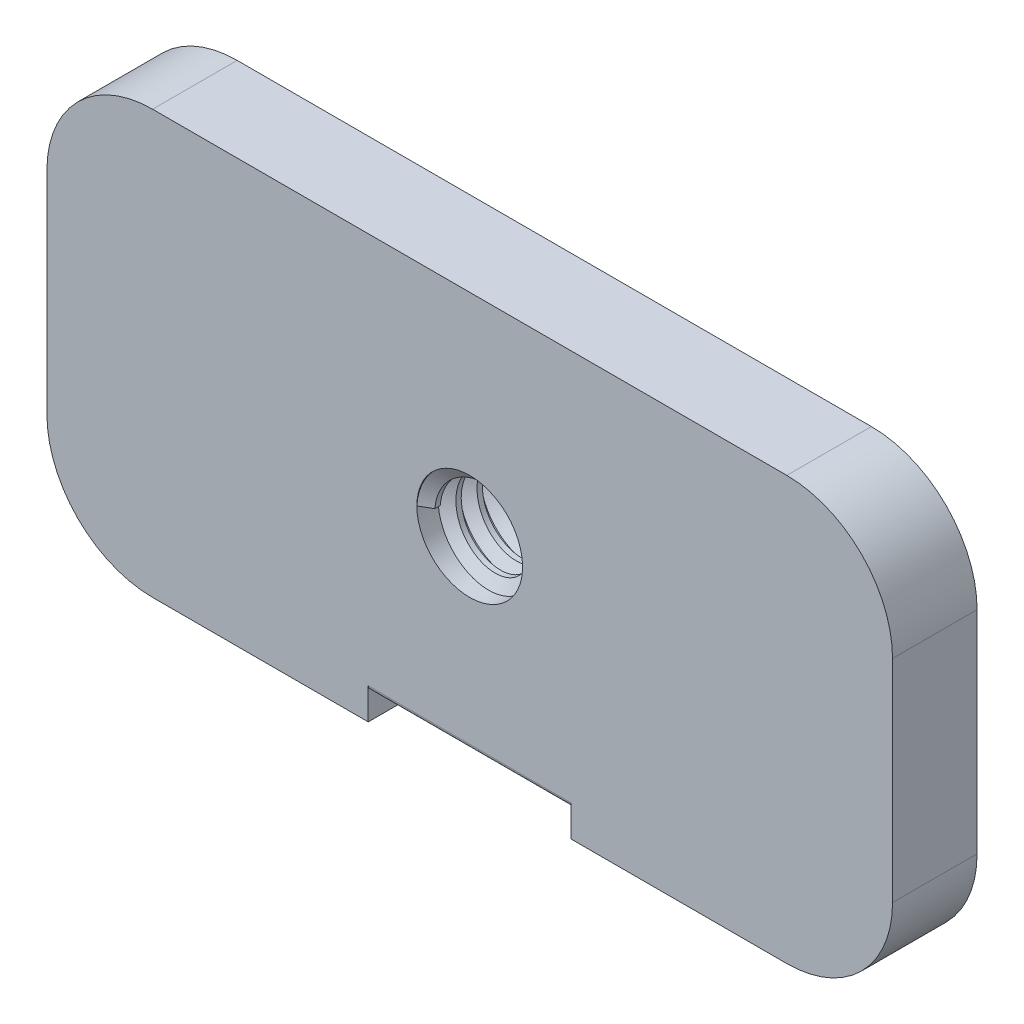
SolidWorks part; units mm, degrees
ref_plane "Front Plane" through (0, 0, 0) normal (0, 0, 1) x (1, 0, 0)
ref_plane "Top Plane" through (0, 0, 0) normal (0, 1, 0) x (1, 0, 0)
ref_plane "Right Plane" through (0, 0, 0) normal (1, 0, 0) x (0, 0, -1)
sketch "Sketch1" plane through (0, 0, 0) normal (0, 0, 1) x (1, 0, 0)
  line L0 (0, -12.7) -> (0, -9.525) construction
  line L1 (-25.4, -12.7) -> (25.4, -12.7)
  line L2 (-25.4, -12.7) -> (-25.4, 12.7)
  line L3 (-25.4, 12.7) -> (25.4, 12.7)
  line L4 (25.4, -12.7) -> (25.4, 12.7)
  line L5 (-25.4, -12.7) -> (25.4, 12.7) construction
  line L6 (-25.4, 12.7) -> (25.4, -12.7) construction
  line L8 (-6.096, -12.7) -> (6.096, -12.7)
  line L9 (-6.096, -12.7) -> (-6.096, -9.525)
  line L10 (-6.096, -9.525) -> (6.096, -9.525)
  line L11 (6.096, -12.7) -> (6.096, -9.525)
  line L12 (-6.096, -12.7) -> (6.096, -9.525) construction
  line L13 (-6.096, -9.525) -> (6.096, -12.7) construction
  circle A0 centre (0, 0) radius 3.175
  point P9 (0, -11.1125)
  dimension "D1" = 6.35
  dimension "D2" = 25.4
  dimension "D3" = 50.8
  dimension "D4" = 3.175
  dimension "D5" = 12.192
extrude "Boss-Extrude1" add sketch "Sketch1" along normal blind 5.08 contours L11 L1 L4 L3 L2 L9 L10 A0 region at (-24.832, 0, 0)
thread "Thread1" pitch 1.27 method extrude profile "Thread Profile1" start angle 0, offset 0, length 0, pitch 1.27, diameter 6.35
ref_plane "Plane1" through (-3.175, 0, 5.08) normal (0, -1, 0) x (-1, 0, 0)
sketch "Thread Profile1" plane through (-3.175, 0, 5.08) normal (0, -1, 0) x (-1, 0, 0)
  line L0 (0, 0) -> (0, 1.27) construction
  line L11 (0, 0) -> (0, 1.1112)
  line L12 (0, 1.1112) -> (-0.6874, 0.7144)
  line L13 (-0.6874, 0.7144) -> (-0.6874, 0.3969)
  line L15 (-0.6874, 0.3969) -> (0, 0)
  line L17 (-0.6874, 0.5556) -> (0, 0.5556) construction
  point P2 (0, 0)
  dimension "Pitch" = 1.27
  dimension "Profile_Angle" = 60
  dimension "Profile_Land" = 0.3175
  dimension "Profile_Height" = 0.6874
fillet "Fillet1" radius 6.35 4 edges at (-25.4, 12.7, 2.54) (-25.4, -12.7, 2.54) (25.4, 12.7, 2.54) (25.4, -12.7, 2.54)
chamfer "Chamfer1" distance 3.175 angle 45 1 edges at (0, -9.525, 0)
sketch "Sketch5" plane through (6.096, 0, 0) normal (-1, 0, 0) x (0, 0, 1)
  line L0 (3.175, -9.525) -> (5.08, -11.43)
  line L1 (5.08, -12.7) -> (5.08, -6.35) construction
  line L2 (3.175, -9.525) -> (0, -6.35) construction
  line L3 (3.175, -9.525) -> (5.08, -9.525)
  line L4 (5.08, -9.525) -> (5.08, -11.43)
  dimension "D1" = 90
extrude "Boss-Extrude2" add sketch "Sketch5" along normal up to next
fillet "Fillet2" radius 0.254 1 edges at (0, -11.43, 5.08)
